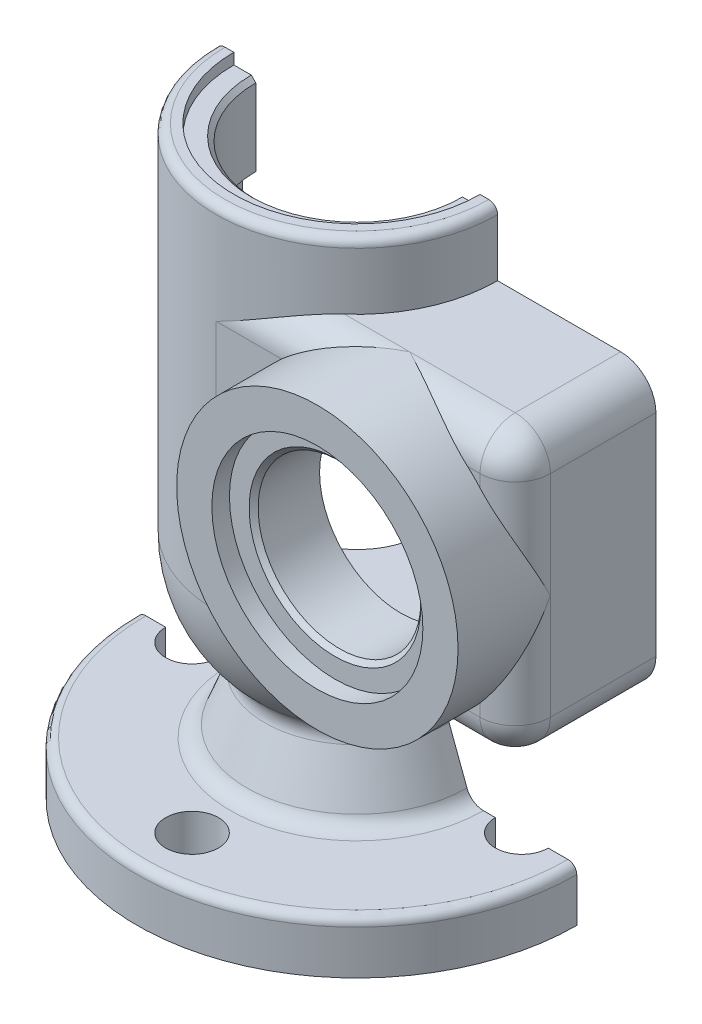
SolidWorks part; units mm, degrees
material "Alloy Steel"
ref_plane "Front Plane" through (0, 0, 0) normal (0, 0, 1) x (1, 0, 0)
ref_plane "Top Plane" through (0, 0, 0) normal (0, 1, 0) x (1, 0, 0)
ref_plane "Right Plane" through (0, 0, 0) normal (1, 0, 0) x (0, 0, -1)
sketch "Sketch1" plane through (0, 0, 0) normal (0, 0, 1) x (1, 0, 0)
  line L0 (0, 0) -> (50, 0)
  line L1 (50, 0) -> (50, 12)
  line L2 (50, 12) -> (26, 12)
  line L3 (26, 12) -> (20, 28)
  line L4 (32, 52.98) -> (32, 133)
  line L5 (32, 133) -> (0, 133)
  line L6 (0, 133) -> (0, 0) construction
  line L7 (0, 0) -> (0, 133)
  arc A0 (20, 28) -> (32, 52.98) centre (0, 52.98) ccw
  dimension "D6" = 32
  dimension "D1" = 133
  dimension "D2" = 40
  dimension "D3" = 52
  dimension "D4" = 12
  dimension "D5" = 100
  dimension "D7" = 28
revolve "Revolve1" add sketch "Sketch1" angle 360 about L6
sketch "Sketch2" plane through (0, 0, 0) normal (0, -1, 0) x (1, 0, 0)
  circle A0 centre (0, 0) radius 30
  dimension "D1" = 60
extrude "Boss-Extrude1" add sketch "Sketch2" along normal blind 2
sketch "Sketch3" plane through (0, 0, 0) normal (1, 0, 0) x (0, 0, -1)
  line L0 (-32, 133) -> (-32, 52.98) construction
  line L1 (32, 118) -> (-32, 118)
  line L2 (32, 118) -> (32, 54)
  line L3 (32, 54) -> (-32, 54)
  line L4 (-32, 118) -> (-32, 54)
  line L5 (32, 118) -> (-32, 54) construction
  line L6 (32, 54) -> (-32, 118) construction
  line L7 (32, 52.98) -> (32, 133) construction
  point P0 (0, 86)
  dimension "D1" = 86
  dimension "D2" = 64
extrude "Boss-Extrude2" add sketch "Sketch3" along normal blind 68
fillet "Fillet1" radius 8 8 edges at (34, 54, -32) (34, 118, -32) (34, 54, 32) (34, 118, 32) (68, 118, 0) (68, 86, -32) (68, 54, 0) (68, 86, 32)
sketch "Sketch4" plane through (0, 0, 32) normal (0, 0, 1) x (1, 0, 0)
  line L0 (68, 110) -> (68, 62) construction
  line L1 (21.166, 118) -> (60, 118) construction
  line L2 (60, 54) -> (21.166, 54) construction
  circle A0 centre (36, 86) radius 32
extrude "Boss-Extrude3" add sketch "Sketch4" along normal blind 13 and the other way up to next
fillet "Fillet2" radius 4 2 edges at (0, 28, 20) (0, 12, 26)
ref_plane "Plane1" through (0, 0, -73) normal (0, 0, 1) x (1, 0, 0)
sketch "Sketch5" plane through (0, 0, -73) normal (0, 0, 1) x (1, 0, 0)
  line L0 (36, 125.9517) -> (36, 86) construction
  line L1 (-2, 86) -> (16, 86) construction
  line L2 (80.6316, 102.7339) -> (47.7895, 115.7491)
  line L3 (80.6316, 69.2661) -> (47.7895, 56.2509)
  line L4 (80.6316, 102.7339) -> (47.7895, 115.7491)
  line L5 (80.6316, 69.2661) -> (47.7895, 56.2509)
  line L6 (-8.6316, 69.2661) -> (24.2105, 56.2509)
  line L7 (-8.6316, 102.7339) -> (24.2105, 115.7491)
  line L8 (16, 86) -> (36, 86) construction
  line L9 (56, 86) -> (74, 86) construction
  line L10 (36, 86) -> (56, 86) construction
  arc A0 (47.7895, 115.7491) -> (24.2105, 115.7491) centre (36, 86) ccw
  arc A1 (80.6316, 69.2661) -> (80.6316, 102.7339) centre (74, 86) ccw
  circle A2 centre (74, 86) radius 6
  circle A3 centre (-2, 86) radius 6
  arc A4 (-8.6316, 69.2661) -> (-8.6316, 102.7339) centre (-2, 86) cw
  arc A5 (64.2105, 101.1052) -> (56, 86) centre (74, 86) ccw construction
  arc A6 (68, 86) -> (64.2105, 101.1052) centre (36, 86) ccw construction
  arc A7 (56, 86) -> (64.2105, 70.8948) centre (74, 86) ccw construction
  arc A8 (64.2105, 70.8948) -> (68, 86) centre (36, 86) ccw construction
  arc A9 (47.7895, 56.2509) -> (64.2105, 70.8948) centre (36, 86) ccw construction
  arc A10 (64.2105, 70.8948) -> (80.6316, 69.2661) centre (74, 86) ccw construction
  arc A11 (24.2105, 115.7491) -> (7.7895, 101.1052) centre (36, 86) ccw construction
  arc A12 (4, 86) -> (7.7895, 70.8948) centre (36, 86) ccw construction
  arc A13 (-8.6316, 102.7339) -> (7.7895, 101.1052) centre (-2, 86) cw construction
  arc A14 (7.7895, 101.1052) -> (4, 86) centre (36, 86) ccw construction
  arc A15 (7.7895, 101.1052) -> (16, 86) centre (-2, 86) cw construction
  arc A16 (16, 86) -> (7.7895, 70.8948) centre (-2, 86) cw construction
  arc A17 (7.7895, 70.8948) -> (24.2105, 56.2509) centre (36, 86) ccw construction
  arc A18 (24.2105, 56.2509) -> (47.7895, 56.2509) centre (36, 86) ccw
  arc A19 (7.7895, 70.8948) -> (-8.6316, 69.2661) centre (-2, 86) cw construction
  arc A20 (64.2105, 101.1052) -> (47.7895, 115.7491) centre (36, 86) ccw construction
  arc A21 (80.6316, 102.7339) -> (64.2105, 101.1052) centre (74, 86) ccw construction
  dimension "D1" = 64
  dimension "D2" = 36
  dimension "D3" = 12
  dimension "D4" = 76
  dimension "D5" = 86
  dimension "D6" = 36
extrude "Boss-Extrude4" add sketch "Sketch5" along normal blind 12 separate body contours L6 A18 L3 A1 L2 A0 L7 A4 A3 A2
sketch "Sketch6" plane through (0, 0, -73) normal (0, 0, -1) x (-1, 0, 0)
  circle A0 centre (-36, 86) radius 24
  dimension "D1" = 48
extrude "Boss-Extrude5" add sketch "Sketch6" along normal blind 2
sketch "Sketch7" plane through (0, 0, -61) normal (0, 0, 1) x (1, 0, 0)
  circle A0 centre (36, 86) radius 26
  dimension "D1" = 52
sketch "Sketch8" plane through (0, 0, -32) normal (0, 0, -1) x (-1, 0, 0)
  circle A0 centre (-36, 86) radius 23
  dimension "D1" = 46
loft "Loft2" add profiles "Sketch7", "Sketch8"
sketch "Sketch11" plane through (0, 0, 0) normal (0, 0, 1) x (1, 0, 0)
  line L0 (68, 62) -> (68, 110) construction
  line L1 (60, 112) -> (0, 112)
  line L2 (62, 110) -> (62, 62)
  line L3 (60, 60) -> (0, 60)
  line L4 (0, 112) -> (0, 60)
  line L5 (60, 118) -> (21.166, 118) construction
  arc A0 (62, 62) -> (60, 60) centre (60, 62) cw
  arc A1 (60, 112) -> (62, 110) centre (60, 110) cw
  point P14 (62, 60)
  point P17 (62, 112)
  dimension "D4" = 2
  dimension "D1" = 52
  dimension "D2" = 6
  dimension "D3" = 6
extrude "Cut-Extrude1" cut sketch "Sketch11" against normal mid plane 52
ref_plane "Plane2" through (0, 86, 0) normal (0, -1, 0) x (-1, 0, 0)
sketch "Sketch13" plane through (0, 86, 0) normal (0, -1, 0) x (-1, 0, 0)
  circle A0 centre (0, 0) radius 26
  circle A1 centre (0, 0) radius 32 construction
  dimension "D1" = 6
extrude "Cut-Extrude2" cut sketch "Sketch13" against normal mid plane 52
sketch "Sketch14" plane through (0, 0, -75) normal (0, 0, -1) x (-1, 0, 0)
  circle A0 centre (-36, 86) radius 18
  dimension "D1" = 36
extrude "Cut-Extrude3" cut sketch "Sketch14" against normal up to next
sketch "Sketch15" plane through (0, 0, 45) normal (0, 0, 1) x (1, 0, 0)
  circle A0 centre (36, 86) radius 24
  dimension "D1" = 48
extrude "Cut-Extrude4" cut sketch "Sketch15" against normal blind 4
hole_wizard "M39x2.0 Tapped Hole1" positions "Sketch18" profile "Sketch19" tap size "M39x2.0" standard "DIN" end condition up to next
sketch "Sketch18" plane through (0, 0, 41) normal (0, 0, 1) x (1, 0, 0)
  point P0 (36, 86)
sketch "Sketch19" plane through (36, 86, 41) normal (1, 0, 0) x (0, -1, 0)
  line L0 (0, 0) -> (0, 15)
  line L1 (0, 15) -> (18.5, 15)
  line L2 (18.5, 15) -> (18.5, 1.025)
  line L3 (18.5, 1.025) -> (19.525, 0)
  line L5 (19.525, 0) -> (0, 0)
  line L6 (-18.5, 1.025) -> (-19.525, 0) construction
  line L11 (0, -6.35) -> (0, 107.95) construction
  dimension "Thru Tap Drill Dia." = 37
  dimension "Thru Tap Drill Depth" = 15
  dimension "Near C'Sink Dia." = 39.05
  dimension "Near C'Sink Angle" = 90
cosmetic thread "Hole Thread1" parameters "D2"=39
sketch "Sketch20" plane through (0, 133, 0) normal (0, 1, 0) x (1, 0, 0)
  circle A0 centre (0, 0) radius 28
  dimension "D1" = 56
extrude "Cut-Extrude5" cut sketch "Sketch20" against normal blind 2.5
hole_wizard "M48x2.0 Tapped Hole1" positions "Sketch21" profile "Sketch22" tap size "M48x2.0" standard "DIN" end condition up to next
sketch "Sketch21" plane through (0, 130.5, 0) normal (0, 1, 0) x (1, 0, 0)
  point P0 (0, 0)
sketch "Sketch22" plane through (0, 130.5, 0) normal (1, 0, 0) x (0, 0, 1)
  line L0 (0, 0) -> (0, 18.5)
  line L1 (0, 18.5) -> (23, 18.5)
  line L2 (23, 18.5) -> (23, 1.025)
  line L3 (23, 1.025) -> (24.025, 0)
  line L5 (24.025, 0) -> (0, 0)
  line L6 (-23, 1.025) -> (-24.025, 0) construction
  line L11 (0, -6.35) -> (0, 107.95) construction
  dimension "Thru Tap Drill Dia." = 46
  dimension "Thru Tap Drill Depth" = 18.5
  dimension "Near C'Sink Dia." = 48.05
  dimension "Near C'Sink Angle" = 90
cosmetic thread "Hole Thread2" parameters "D2"=48
sketch "Sketch23" plane through (0, 0, 0) normal (0, 0, 1) x (1, 0, 0)
  line L0 (0, -2) -> (0, 44) construction
  line L1 (-30, -2) -> (30, -2) construction
  line L2 (0, 44) -> (18, 44)
  line L3 (18, 44) -> (18, 34)
  line L4 (18, 34) -> (12.5, 34)
  line L5 (12.5, 34) -> (12.5, -2)
  line L6 (12.5, -2) -> (0, -2)
  line L7 (0, -2) -> (0, 44)
  dimension "D1" = 10
  dimension "D2" = 25
  dimension "D3" = 36
  dimension "D4" = 36
revolve "Cut-Revolve1" cut sketch "Sketch23" angle 360 about L0
hole_wizard "M33x2.0 Tapped Hole1" positions "Sketch24" profile "Sketch25" tap size "M33x2.0" standard "DIN" end condition up to next
sketch "Sketch24" plane through (0, 44, 0) normal (0, -1, 0) x (1, 0, 0)
  point P0 (0, 0)
sketch "Sketch25" plane through (0, 44, 0) normal (1, 0, 0) x (0, 0, -1)
  line L0 (0, 0) -> (0, 16)
  line L1 (0, 16) -> (15.5, 16)
  line L2 (15.5, 16) -> (15.5, 1.025)
  line L3 (15.5, 1.025) -> (16.525, 0)
  line L5 (16.525, 0) -> (0, 0)
  line L6 (-15.5, 1.025) -> (-16.525, 0) construction
  line L11 (0, -6.35) -> (0, 107.95) construction
  dimension "Thru Tap Drill Dia." = 31
  dimension "Thru Tap Drill Depth" = 16
  dimension "Near C'Sink Dia." = 33.05
  dimension "Near C'Sink Angle" = 90
cosmetic thread "Hole Thread3" parameters "D2"=33
fillet "Fillet3" radius 2 23 edges at (92, 86, -61) (64.2105, 62.7585, -61) (36, 54, -61) (7.7895, 62.7585, -61) (-20, 86, -61) (7.7895, 109.2415, -61) (36, 118, -61) (30, 60, 26) (61.4142, 60.5858, 26) (62, 86, 26) (61.4142, 111.4142, 26) (30, 112, 26) (-26, 112, 0) (30, 112, -26) (61.4142, 111.4142, -26) (62, 86, -26) (61.4142, 60.5858, -26) (30, 60, -26) (0, 12, 50) (0, 133, 32) (64.2105, 109.2415, -61) (62, 86, -61) (-26, 60, 0)
sketch "Sketch26" plane through (0, 12, 0) normal (0, 1, 0) x (1, 0, 0)
  circle A0 centre (0, 0) radius 37.5 construction
  circle A1 centre (0, 37.5) radius 6
  circle A2 centre (37.5, 0) radius 6
  circle A3 centre (0, -37.5) radius 6
  circle A4 centre (-37.5, 0) radius 6
  point P14 (0, 0)
  dimension "D1" = 75
  dimension "D2" = 12
  dimension "D3" = 4
extrude "Cut-Extrude6" cut sketch "Sketch26" against normal through all
split "Split1" trim tools "Front Plane" bodies to split 118 resulting bodies 120
